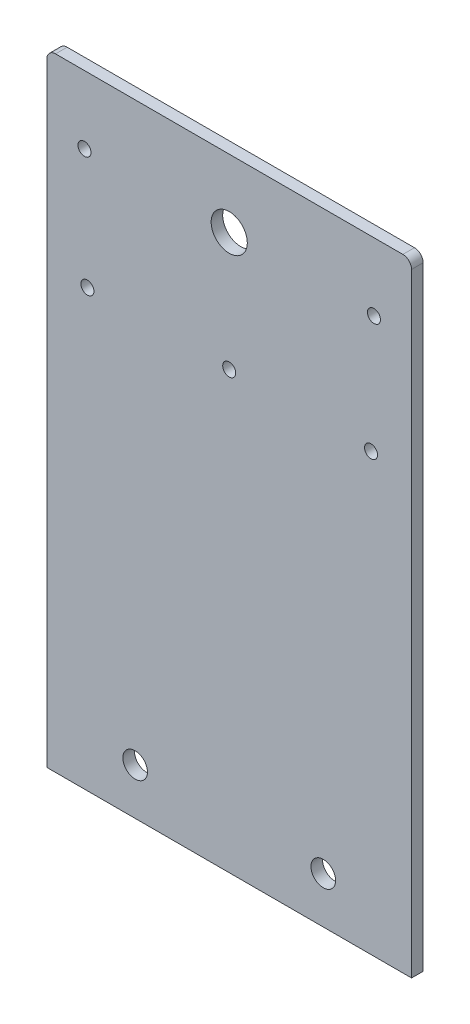
SolidWorks part; units mm, degrees
ref_plane "Ön Düzlem" through (0, 0, 0) normal (0, 0, 1) x (1, 0, 0)
ref_plane "Üst Düzlem" through (0, 0, 0) normal (0, 1, 0) x (1, 0, 0)
ref_plane "Sağ Düzlem" through (0, 0, 0) normal (1, 0, 0) x (0, 0, -1)
sketch "Model" plane through (0, 0, 0) normal (0, 0, 1) x (1, 0, 0)
  line L0 (2223.2213, 1699.5004) -> (2349.2213, 1699.5004)
  line L1 (2349.2213, 1699.5004) -> (2349.2213, 1914.5004)
  line L2 (2349.2213, 1914.5004) -> (2223.2213, 1914.5004)
  line L3 (2223.2213, 1914.5004) -> (2223.2213, 1699.5004)
  circle A0 centre (2253.7663, 1716.3909) radius 4.5
  circle A1 centre (2318.7663, 1716.3909) radius 4.5
  circle A2 centre (2286.2213, 1891.0768) radius 6.25
  circle A3 centre (2236.2213, 1891.0768) radius 2.25
  circle A4 centre (2336.2213, 1891.0768) radius 2.25
  circle A5 centre (2237.2213, 1850.0771) radius 2.25
  circle A6 centre (2286.2213, 1850.0771) radius 2.25
  circle A7 centre (2335.2213, 1850.0771) radius 2.25
base flange "Taban-Flanş1" sketch "Model" thickness 4 reverse thickness direction no parameters "D1"=1.5
sketch "Çizim1" plane through (0, 0, 0) normal (0, 0, 1) x (1, 0, 0)
  line L1 (2230.692, 1735.1208) -> (2336.8147, 1735.1208)
  line L2 (2230.692, 1735.1208) -> (2230.692, 1705.5051)
  line L3 (2230.692, 1705.5051) -> (2336.8147, 1705.5051)
  line L4 (2336.8147, 1735.1208) -> (2336.8147, 1705.5051)
  line L5 (2230.692, 1735.1208) -> (2336.8147, 1705.5051) construction
  line L6 (2230.692, 1705.5051) -> (2336.8147, 1735.1208) construction
  point P0 (2283.7534, 1720.3129)
base flange "Sekme1" sketch "Çizim1" thickness 4 reverse thickness direction no parameters "D1"=1.5
sketch "Çizim4" plane through (0, 0, 0) normal (0, 0, 1) x (1, 0, 0)
  line L0 (2253.7213, 1715.5004) -> (2318.7213, 1715.5004) construction
  line L1 (2223.2213, 1699.5004) -> (2349.2213, 1699.5004) construction
  line L2 (2286.2213, 1715.5004) -> (2286.2213, 1699.5004) construction
  circle A0 centre (2253.7213, 1715.5004) radius 4.25
  circle A1 centre (2318.7213, 1715.5004) radius 4.25
  dimension "D3" = 8.5
  dimension "D1" = 16
  dimension "D2" = 65
extrude "Kes-Ekstrüzyon1" cut sketch "Çizim4" against normal blind 10 normal cut yes
fillet "Radyus1" radius 3 2 edges at (2349.2213, 1914.5004, -2) (2223.2213, 1914.5004, -2)
sketch "Büküm-Çizgileri1" [suppressed] plane through (0, 0, 0) normal (0, 1, 0) x (1, 0, 0)
sketch "Sınırlandırma-Kutusu1" [suppressed] plane through (0, 0, 0) normal (0, 1, 0) x (1, 0, 0)
sheet metal parameters "Sac-Levha1" thickness 4 parameters "D1"=1.5
flat pattern "Düz-Çoğaltma1" [suppressed]
sketch "Büküm-Çizgileri2" plane through (0, 0, 0) normal (0, 1, 0) x (1, 0, 0)
sketch3d "Sınırlandırma-Kutusu2" [suppressed]
  line L0 (-2349.2213, 1914.5004, 0) -> (-2349.2213, 1699.5004, 0) construction
  line L1 (-2223.2213, 1914.5004, 0) -> (-2223.2213, 1699.5004, 0) construction
  line L2 (-2349.2213, 1914.5004, 0) -> (-2223.2213, 1914.5004, 0) construction
  line L3 (-2349.2213, 1699.5004, 0) -> (-2223.2213, 1699.5004, 0) construction
sheet metal parameters "Sac-Levha2" thickness 4 parameters "D1"=1.5
flat pattern "Düz-Çoğaltma2"
sketch "Büküm-Çizgileri3" plane through (0, 0, 0) normal (0, 1, 0) x (1, 0, 0)
sketch3d "Sınırlandırma-Kutusu3" [suppressed]
  line L0 (2349.2213, 1914.5004, 0) -> (2349.2213, 1699.5004, 0) construction
  line L1 (2223.2213, 1914.5004, 0) -> (2223.2213, 1699.5004, 0) construction
  line L2 (2349.2213, 1914.5004, 0) -> (2223.2213, 1914.5004, 0) construction
  line L3 (2349.2213, 1699.5004, 0) -> (2223.2213, 1699.5004, 0) construction
sheet metal parameters "Sac-Levha3" thickness 4 parameters "D1"=1.5
flat pattern "Düz-Çoğaltma2"
sketch "Büküm-Çizgileri3" plane through (0, 0, 0) normal (0, 1, 0) x (1, 0, 0)
sketch3d "Sınırlandırma-Kutusu3" [suppressed]
  line L0 (2349.2213, 1699.5004, 0) -> (2349.2213, 1914.5004, 0) construction
  line L1 (2223.2213, 1699.5004, 0) -> (2223.2213, 1914.5004, 0) construction
  line L2 (2349.2213, 1699.5004, 0) -> (2223.2213, 1699.5004, 0) construction
  line L3 (2349.2213, 1914.5004, 0) -> (2223.2213, 1914.5004, 0) construction
